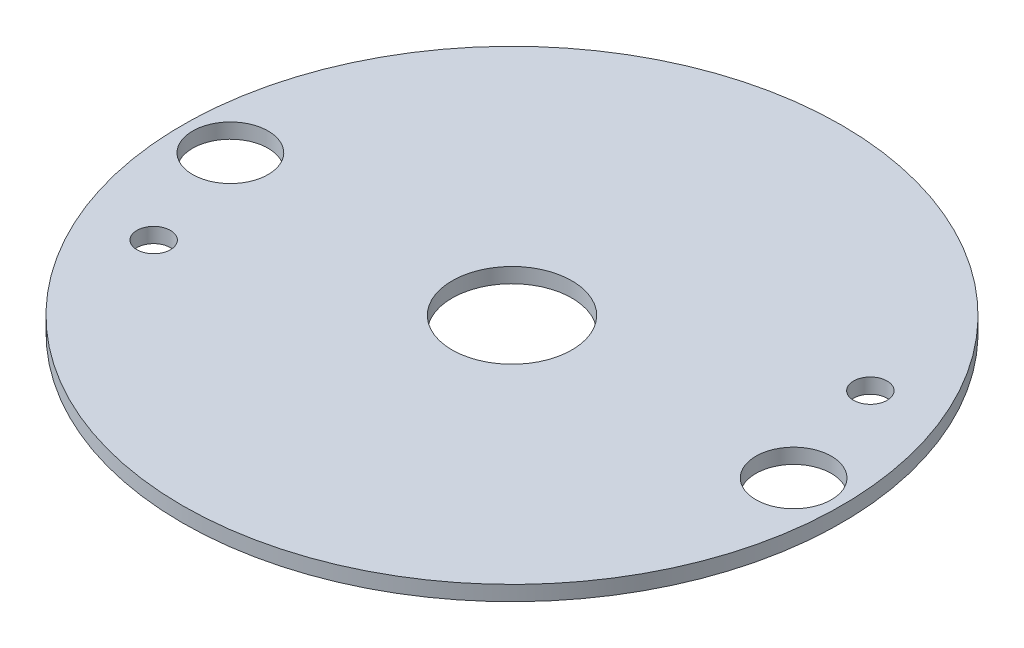
SolidWorks part; units mm, degrees
ref_plane "Front Plane" through (0, 0, 0) normal (0, 0, 1) x (1, 0, 0)
ref_plane "Top Plane" through (0, 0, 0) normal (0, 1, 0) x (1, 0, 0)
ref_plane "Right Plane" through (0, 0, 0) normal (1, 0, 0) x (0, 0, -1)
sketch "Sketch1" plane through (0, 0, 0) normal (0, 1, 0) x (1, 0, 0)
  circle A0 centre (0, 0) radius 69.85
  circle A1 centre (0, 0) radius 12.7
extrude "Boss-Extrude1" add sketch "Sketch1" along normal blind 3.175
sketch "Sketch2" plane through (0, 3.175, 0) normal (0, 1, 0) x (1, 0, 0)
  line L0 (59.69, 0) -> (-59.69, 0) construction
  line L1 (51.7955, 24.1526) -> (-51.7955, -24.1526) construction
  circle A0 centre (-59.69, 0) radius 8.001
  circle A1 centre (59.69, 0) radius 8.001
  circle A2 centre (-51.7955, -24.1526) radius 3.556
  circle A3 centre (51.7955, 24.1526) radius 3.556
  point P4 (0, 0)
  point P8 (0, 0)
extrude "Cut-Extrude1" cut sketch "Sketch2" against normal blind 3.175
